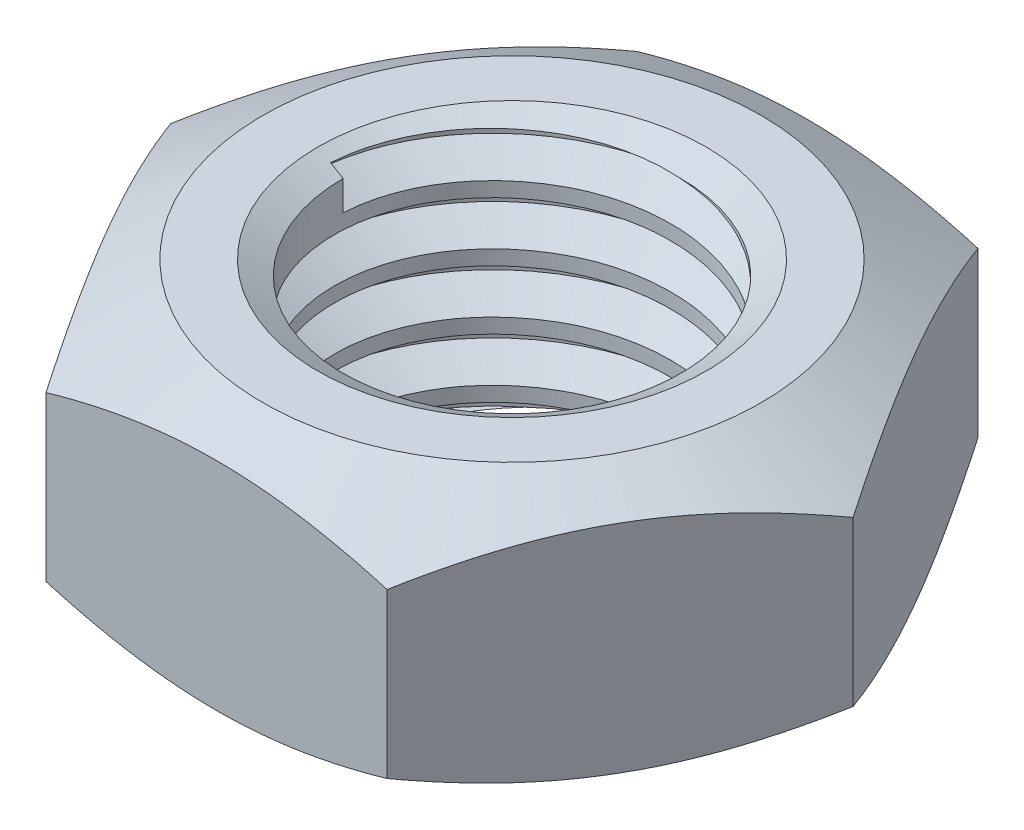
SolidWorks part; units mm, degrees
ref_plane "Alzado" through (0, 0, 0) normal (0, 0, 1) x (1, 0, 0)
ref_plane "Planta" through (0, 0, 0) normal (0, 1, 0) x (1, 0, 0)
ref_plane "Vista lateral" through (0, 0, 0) normal (1, 0, 0) x (0, 0, -1)
sketch "Croquis1" plane through (0, 0, 0) normal (0, 1, 0) x (1, 0, 0)
  line L1 (4.0415, 0) -> (2.0207, 3.5)
  line L2 (2.0207, 3.5) -> (-2.0207, 3.5)
  line L3 (-2.0207, 3.5) -> (-4.0415, 0)
  line L4 (-4.0415, 0) -> (-2.0207, -3.5)
  line L5 (-2.0207, -3.5) -> (2.0207, -3.5)
  line L6 (2.0207, -3.5) -> (4.0415, 0)
  circle A0 centre (0, 0) radius 3.5 construction
  dimension "D1" = 7
extrude "Saliente-Extruir1" add sketch "Croquis1" along normal mid plane 3.2
sketch "Croquis2" plane through (0, 0, 0) normal (0, 1, 0) x (1, 0, 0)
  circle A0 centre (0, 0) radius 2
  dimension "D1" = 4
extrude "Cortar-Extruir1" cut sketch "Croquis2" against normal through all both and the other way through all
ref_axis "Eje1" through (0, -1.6, 0) along (0, 1, 0)
thread "Rosca1" pitch 0.7 method cut profile "Perfil de rosca1" start angle 0, offset 0, length 0, pitch 0.7, diameter 4
ref_plane "Plano1" through (-2, 1.6, 0) normal (0, 0, 1) x (-1, 0, 0)
sketch "Perfil de rosca1" plane through (-2, 1.6, 0) normal (0, 0, 1) x (-1, 0, 0)
  line L0 (0, 0) -> (0, 0.7) construction
  line L1 (0, 0) -> (0.3789, 0.2187)
  line L2 (0.3789, 0.2187) -> (0.3789, 0.3062)
  line L3 (0.3789, 0.3062) -> (0, 0.525)
  line L4 (0.3789, 0.2625) -> (0, 0.2625) construction
  line L11 (0, 0) -> (0, 0.525)
  point P2 (0, 0)
  dimension "Pitch" = 0.7
  dimension "Profile_Angle" = 60
  dimension "Profile_Land" = 0.0875
  dimension "Profile_Height" = 0.3789
sketch "Croquis6" plane through (0, 0, 0) normal (0, 0, 1) x (1, 0, 0)
  line L0 (2.95, 1.6) -> (4.0415, 0.9698)
  line L1 (2.0207, 1.6) -> (4.0415, 1.6) construction
  line L2 (4.0415, 1.6) -> (4.0415, -1.6) construction
  line L3 (0, -1.9538) -> (0, 1.9538) construction
  line L4 (2, 1.4268) -> (2.3, 1.6)
  line L5 (2, 1.25) -> (2, 1.6) construction
  spline S0 degree 3 poles (2.95, 1.6) (4.4668, 6.8368) (8.4115, -0.3503) (4.0415, 0.9698) knots 0 0 0 0 1 1 1 1
  spline S1 degree 3 poles (2, 1.4268) (-2.6115, 2.2018) (3.2536, 4.3268) (2.3, 1.6) knots 0 0 0 0 1 1 1 1
  dimension "D1" = 2.95
  dimension "D2" = 30
  dimension "D3" = 2.3
  dimension "D4" = 60
revolve "Cortar-Revolución1" cut sketch "Croquis6" angle 360 about axis through (0, -1.6, 0) along (0, 1, 0)
mirror "Simetría1" about plane through (0, 0, 0) normal (0, 1, 0) of "Cortar-Revolución1"
